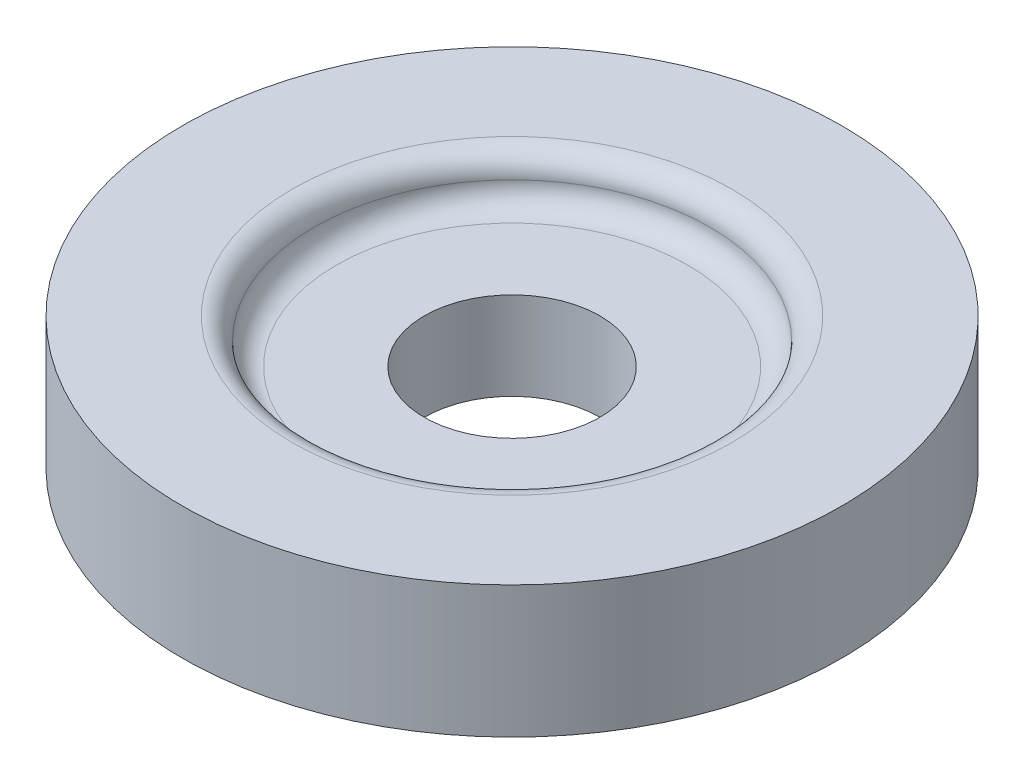
SolidWorks part; units mm, degrees
ref_plane "前视基准面" through (0, 0, 0) normal (0, 0, 1) x (1, 0, 0)
ref_plane "上视基准面" through (0, 0, 0) normal (0, 1, 0) x (1, 0, 0)
ref_plane "右视基准面" through (0, 0, 0) normal (1, 0, 0) x (0, 0, -1)
sketch "草图2" plane through (0, 0, 0) normal (0, 0, 1) x (1, 0, 0)
  line L0 (0, 0) -> (0, 9.2619) construction
  line L1 (2, 0) -> (7.5, 0)
  line L2 (7.5, 0) -> (7.5, 3)
  line L3 (7.5, 3) -> (4.5, 3)
  line L4 (4.5, 3) -> (4.5, 2)
  line L5 (4.5, 2) -> (2, 2)
  line L6 (2, 2) -> (2, 0)
  point P7 (1.128, 0)
  dimension "D1" = 3
  dimension "D2" = 15
  dimension "D3" = 4
  dimension "D4" = 1
  dimension "D5" = 3
revolve "旋转1" add sketch "草图2" angle 360 about L0
fillet "圆角1" radius 0.5 2 edges at (0, 2, -4.5) (0, 3, -4.5)
